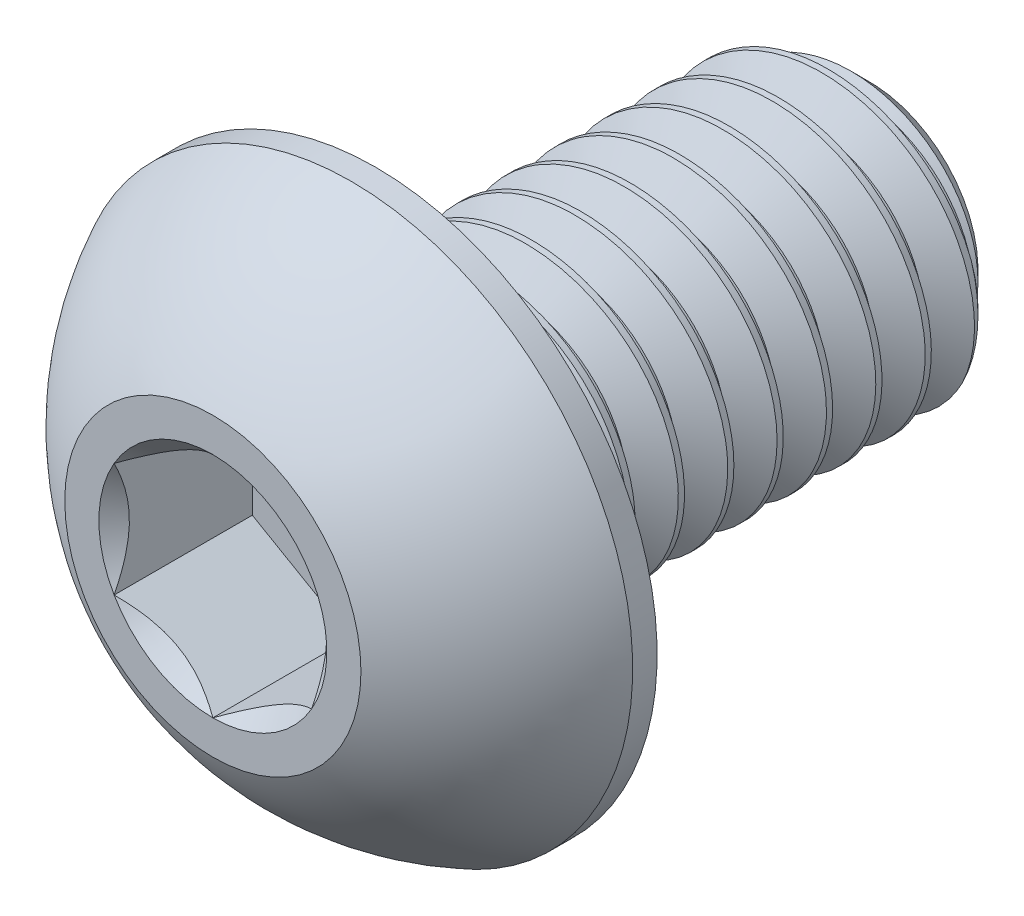
SolidWorks part; units mm, degrees
ref_plane "Front Plane" through (0, 0, 0) normal (0, 0, 1) x (1, 0, 0)
ref_plane "Top Plane" through (0, 0, 0) normal (0, 1, 0) x (1, 0, 0)
ref_plane "Right Plane" through (0, 0, 0) normal (1, 0, 0) x (0, 0, -1)
sketch "Sketch1" plane through (0, 0, 0) normal (1, 0, 0) x (0, 0, -1)
  line L0 (-3.325, 0) -> (3.325, 0) construction
  line L1 (-1.675, 2.85) -> (-1.675, -2.85) construction
  line L2 (3.325, 1.5) -> (3.325, -1.5) construction
  line L3 (3.2938, 1.5541) -> (3.5438, 1.1211) construction
  line L4 (3.5438, 1.1211) -> (3.7938, 1.5541) construction
  line L5 (3.7938, 1.5541) -> (3.2938, 1.5541) construction
  line L6 (3.325, 1.5) -> (3.7625, 1.5) construction
  line L7 (3.5438, 1.5541) -> (3.5438, 1.5) construction
  line L8 (3.5438, 1.5) -> (3.5438, 1.1752) construction
  line L9 (3.5438, 1.1752) -> (3.5438, 1.1211) construction
  line L10 (3.5125, 1.1752) -> (3.575, 1.1752)
  line L11 (3.3094, 1.5271) -> (3.7781, 1.5271)
  line L12 (3.575, 1.1752) -> (3.7781, 1.5271)
  line L13 (3.5125, 1.1752) -> (3.3094, 1.5271)
  line L14 (-3.325, 1) -> (-3.325, -1) construction
  line L15 (3.325, 1.5) -> (-1.675, 1.5) construction
  point P3 (-1.675, 0)
  point P6 (-1.925, 0)
  point P21 (3.5438, 1.5271)
  point P24 (-1.9225, 2.85)
  point P25 (2.075, -1.5)
  point P26 (-3.325, 1.5)
  dimension "Head Height" = 1.65
  dimension "Mounting Fastener Thread Length" = 5
  dimension "Head Dia" = 5.7
  dimension "Mounting Fastener Thread Size" = 3
  dimension "Pitch" = 0.5
  dimension "Drive Size" = 2
  dimension "D1" = 1.4
  dimension "D4" = 1.25
sketch "Sketch2" plane through (0, 0, 0) normal (1, 0, 0) x (0, 0, -1)
  line L0 (-3.325, 0) -> (3.325, 0)
  line L1 (3.325, 0) -> (3.325, 1.1)
  line L2 (3.325, 1.5) -> (3.325, -1.5) construction
  line L3 (3.325, 1.1) -> (2.925, 1.5)
  line L4 (2.925, 1.5) -> (-1.675, 1.5)
  line L5 (-1.675, 2.85) -> (-1.675, -2.85) construction
  line L6 (-1.675, 1.5) -> (-1.675, 2.85)
  line L7 (-1.675, 2.85) -> (-1.9225, 2.85)
  line L8 (3.325, 1.5) -> (3.7625, 1.5) construction
  line L9 (-3.325, 0) -> (-3.325, 1.5)
  arc A0 (-3.325, 1.5) -> (-1.9225, 2.85) centre (-0.5302, 0) cw
  dimension "D1" = 0.4
  dimension "D2" = 45
revolve "Revolve1" add sketch "Sketch2" angle 360 about L0
sketch "Sketch3" plane through (0, 0, 3.325) normal (0, 0, 1) x (1, 0, 0)
  line L1 (0, 1.1547) -> (-1, 0.5774)
  line L2 (-1, 0.5774) -> (-1, -0.5774)
  line L3 (-1, -0.5774) -> (0, -1.1547)
  line L4 (0, -1.1547) -> (1, -0.5774)
  line L5 (1, -0.5774) -> (1, 0.5774)
  line L6 (1, 0.5774) -> (0, 1.1547)
  circle A0 centre (0, 0) radius 1 construction
  dimension "D1" = 2
extrude "Cut-Extrude1" cut sketch "Sketch3" against normal up to vertex (1.4 mm away) up to point (0, 0, 1.925)
sketch "Sketch4" plane through (0, 0, 3.325) normal (0, 0, 1) x (1, 0, 0)
  circle A0 centre (0, 0) radius 1.1547
extrude "Cut-Extrude2" cut sketch "Sketch4" against normal blind 10 draft 45
split "Split1" bodies to split 106 resulting bodies 107 108 split by face at (0, -2.85, 1.675)
sketch "Sketch5" plane through (0, 0, -3.325) normal (0, 0, -1) x (-1, 0, 0)
  circle A0 centre (0, 0) radius 1.5 construction
  circle A1 centre (0, 0) radius 1.5
curve "Helix/Spiral1" pitch 0.5 height 5.5 radius 1.5 centre (0, 0, -3.325) axis (0, 0, 1) start towards (0, 1, 0)
sketch "Sketch6" plane through (0, 0, 0) normal (1, 0, 0) x (0, 0, -1)
  line L0 (3.5125, 1.1752) -> (3.575, 1.1752) construction
  line L1 (3.5125, 1.1752) -> (3.3094, 1.5271) construction
  line L2 (3.3094, 1.5271) -> (3.7781, 1.5271) construction
  line L3 (3.575, 1.1752) -> (3.7781, 1.5271) construction
  line L4 (3.5125, 1.1752) -> (3.575, 1.1752)
  line L5 (3.5125, 1.1752) -> (3.3094, 1.5271)
  line L6 (3.3094, 1.5271) -> (3.7781, 1.5271)
  line L7 (3.575, 1.1752) -> (3.7781, 1.5271)
sweep "Cut-Sweep1" cut profiles "Sketch6" path "Helix/Spiral1" align with end faces yes
sketch "Sketch7" plane through (0, 0, 1.675) normal (0, 0, -1) x (-1, 0, 0)
  circle A1 centre (0, 0) radius 1.5
  circle A2 centre (0, 0) radius 1.5
  dimension "D1" = 0
extrude "Boss-Extrude1" add sketch "Sketch7" along normal blind 10 draft 30
equation "\"D2@Sketch1\" = \"Pitch@Sketch1\" / 8"
equation "\"D1@Sketch1\"=\"Drive Size@Sketch1\"*.7"
equation "\"D3@Sketch1\"=\"Head Height@Sketch1\"*.15"
equation "\"D1@Sketch2\"=\"Pitch@Sketch1\"*.8"
equation "\"D1@Sketch3\"=\"Drive Size@Sketch1\""
equation "\"D4@Helix/Spiral1\"=\"Pitch@Sketch1\""
equation "\"D3@Helix/Spiral1\" = \"Mounting Fastener Thread Length@Sketch1\" + \"Pitch@Sketch1\""
equation "\"D4@Sketch1\"=\"Pitch@Sketch1\"*2.5"
